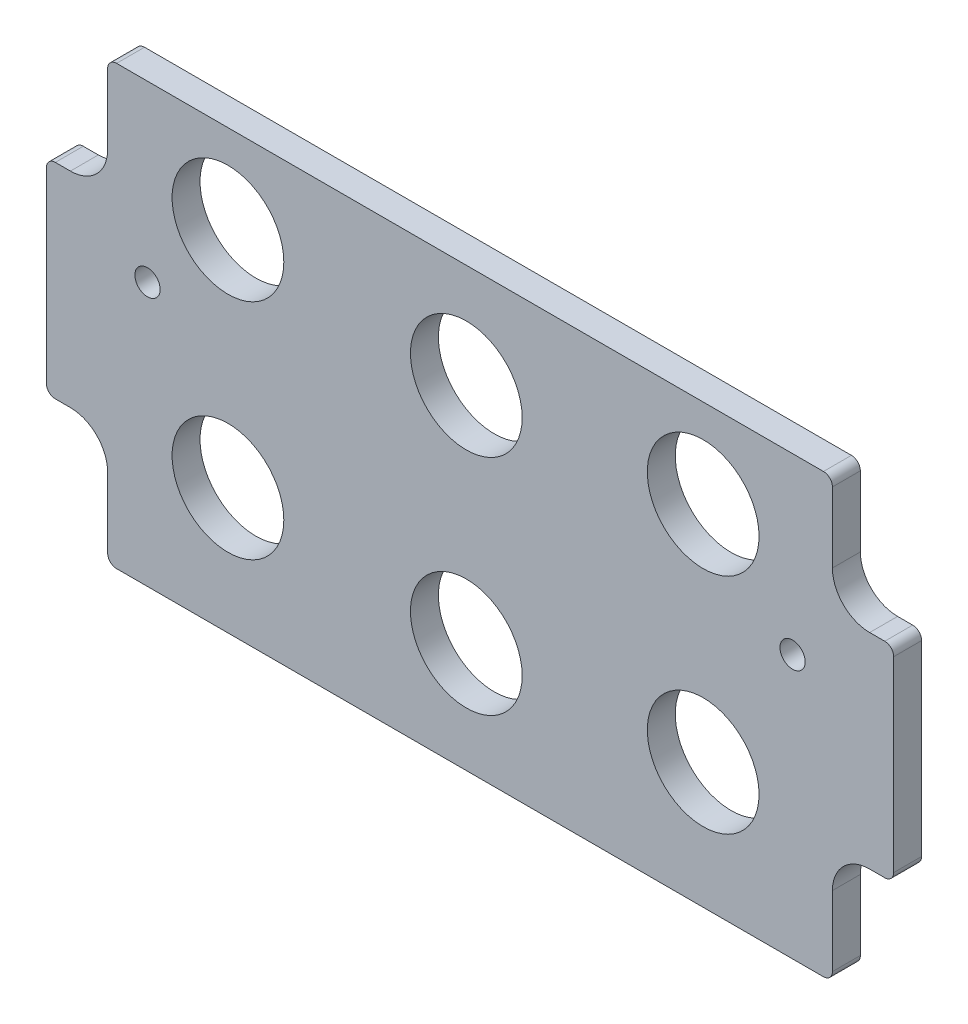
SolidWorks part; units mm, degrees
ref_plane "Front Plane" through (0, 0, 0) normal (0, 0, 1) x (1, 0, 0)
ref_plane "Top Plane" through (0, 0, 0) normal (0, 1, 0) x (1, 0, 0)
ref_plane "Right Plane" through (0, 0, 0) normal (1, 0, 0) x (0, 0, -1)
sketch "Sketch1" plane through (0, 0, 0) normal (0, 0, 1) x (1, 0, 0)
  line L12 (134.8105, 61.9125) -> (134.8105, 73.8822)
  line L13 (133.2865, 75.4062) -> (12.7635, 75.4062)
  line L14 (11.2395, 73.8822) -> (11.2395, 61.9125)
  line L15 (4.8895, 55.5625) -> (2.3178, 55.5625)
  line L16 (0.7938, 54.0385) -> (0.7938, 22.1615)
  line L17 (2.3178, 20.6375) -> (4.8895, 20.6375)
  line L18 (11.2395, 14.2875) -> (11.2395, 2.3178)
  line L19 (12.7635, 0.7938) -> (133.2865, 0.7937)
  line L20 (134.8105, 2.3177) -> (134.8105, 14.2875)
  line L21 (141.1605, 20.6375) -> (143.7323, 20.6375)
  line L22 (145.2563, 22.1615) -> (145.2563, 54.0385)
  line L23 (143.7323, 55.5625) -> (141.1605, 55.5625)
  line L24 (134.8105, 61.9125) -> (134.8105, 73.8822)
  line L25 (133.2865, 75.4062) -> (12.7635, 75.4062)
  line L26 (11.2395, 73.8822) -> (11.2395, 61.9125)
  line L27 (4.8895, 55.5625) -> (2.3178, 55.5625)
  line L28 (0.7938, 54.0385) -> (0.7938, 22.1615)
  line L29 (2.3178, 20.6375) -> (4.8895, 20.6375)
  line L30 (11.2395, 14.2875) -> (11.2395, 2.3178)
  line L31 (12.7635, 0.7938) -> (133.2865, 0.7937)
  line L32 (134.8105, 2.3177) -> (134.8105, 14.2875)
  line L33 (141.1605, 20.6375) -> (143.7323, 20.6375)
  line L34 (145.2563, 22.1615) -> (145.2563, 54.0385)
  line L35 (143.7323, 55.5625) -> (141.1605, 55.5625)
  arc A12 (134.8105, 61.9125) -> (141.1605, 55.5625) centre (141.1605, 61.9125) ccw
  arc A13 (134.8105, 73.8822) -> (133.2865, 75.4062) centre (133.2865, 73.8822) ccw
  arc A14 (12.7635, 75.4062) -> (11.2395, 73.8822) centre (12.7635, 73.8822) ccw
  arc A15 (4.8895, 55.5625) -> (11.2395, 61.9125) centre (4.8895, 61.9125) ccw
  arc A16 (2.3178, 55.5625) -> (0.7938, 54.0385) centre (2.3178, 54.0385) ccw
  arc A17 (0.7938, 22.1615) -> (2.3178, 20.6375) centre (2.3178, 22.1615) ccw
  arc A18 (11.2395, 14.2875) -> (4.8895, 20.6375) centre (4.8895, 14.2875) ccw
  arc A19 (11.2395, 2.3178) -> (12.7635, 0.7938) centre (12.7635, 2.3178) ccw
  arc A20 (133.2865, 0.7937) -> (134.8105, 2.3177) centre (133.2865, 2.3177) ccw
  arc A21 (141.1605, 20.6375) -> (134.8105, 14.2875) centre (141.1605, 14.2875) ccw
  arc A22 (143.7323, 20.6375) -> (145.2563, 22.1615) centre (143.7323, 22.1615) ccw
  arc A23 (145.2563, 54.0385) -> (143.7323, 55.5625) centre (143.7323, 54.0385) ccw
  arc A24 (134.8105, 61.9125) -> (141.1605, 55.5625) centre (141.1605, 61.9125) ccw
  arc A25 (134.8105, 73.8822) -> (133.2865, 75.4062) centre (133.2865, 73.8822) ccw
  arc A26 (12.7635, 75.4062) -> (11.2395, 73.8822) centre (12.7635, 73.8822) ccw
  arc A27 (4.8895, 55.5625) -> (11.2395, 61.9125) centre (4.8895, 61.9125) ccw
  arc A28 (2.3178, 55.5625) -> (0.7938, 54.0385) centre (2.3178, 54.0385) ccw
  arc A29 (0.7938, 22.1615) -> (2.3178, 20.6375) centre (2.3178, 22.1615) ccw
  arc A30 (11.2395, 14.2875) -> (4.8895, 20.6375) centre (4.8895, 14.2875) ccw
  arc A31 (11.2395, 2.3178) -> (12.7635, 0.7938) centre (12.7635, 2.3178) ccw
  arc A32 (133.2865, 0.7937) -> (134.8105, 2.3177) centre (133.2865, 2.3177) ccw
  arc A33 (141.1605, 20.6375) -> (134.8105, 14.2875) centre (141.1605, 14.2875) ccw
  arc A34 (143.7323, 20.6375) -> (145.2563, 22.1615) centre (143.7323, 22.1615) ccw
  arc A35 (145.2563, 54.0385) -> (143.7323, 55.5625) centre (143.7323, 54.0385) ccw
  dimension "D1" = 0
extrude "Boss-Extrude1" add sketch "Sketch1" along normal blind 4.7625
hole_wizard "3/4 (0.75) Diameter Hole1" positions "Sketch3" profile "Sketch2" hole size "3/4" standard "ANSI Inch" end condition through all
sketch "Sketch3" plane through (0, 0, 4.7625) normal (0, 0, 1) x (1, 0, 0)
  point P0 (31.75, 60.325)
  point P4 (72.39, 57.658)
  point P7 (112.776, 60.325)
  point P10 (112.776, 22.225)
  point P13 (31.75, 22.225)
  point P18 (72.39, 19.558)
sketch "Sketch2" plane through (31.75, 60.325, 4.7625) normal (1, 0, 0) x (0, -1, 0)
  line L0 (0, 0) -> (0, 4.7625)
  line L1 (0, 4.7625) -> (9.525, 4.7625)
  line L2 (9.525, 4.7625) -> (9.525, 0)
  line L5 (9.525, 0) -> (0, 0)
  line L11 (0, -6.35) -> (0, 107.95) construction
  dimension "Thru Hole Dia." = 19.05
  dimension "Thru Hole Depth" = 4.7625
hole_wizard "#6 Clearance Hole1" positions "Sketch5" profile "Sketch4" hole size "#6" standard "ANSI Inch" end condition through all
sketch "Sketch5" plane through (0, 0, 4.7625) normal (0, 0, 1) x (1, 0, 0)
  point P0 (18.034, 45.72)
  point P3 (128.016, 45.72)
sketch "Sketch4" plane through (18.034, 45.72, 4.7625) normal (1, 0, 0) x (0, -1, 0)
  line L0 (0, 0) -> (0, 4.7625)
  line L1 (0, 4.7625) -> (2.1526, 4.7625)
  line L2 (2.1526, 4.7625) -> (2.1526, 0)
  line L5 (2.1526, 0) -> (0, 0)
  line L11 (0, -6.35) -> (0, 107.95) construction
  dimension "Thru Hole Dia." = 4.3053
  dimension "Thru Hole Depth" = 4.7625
